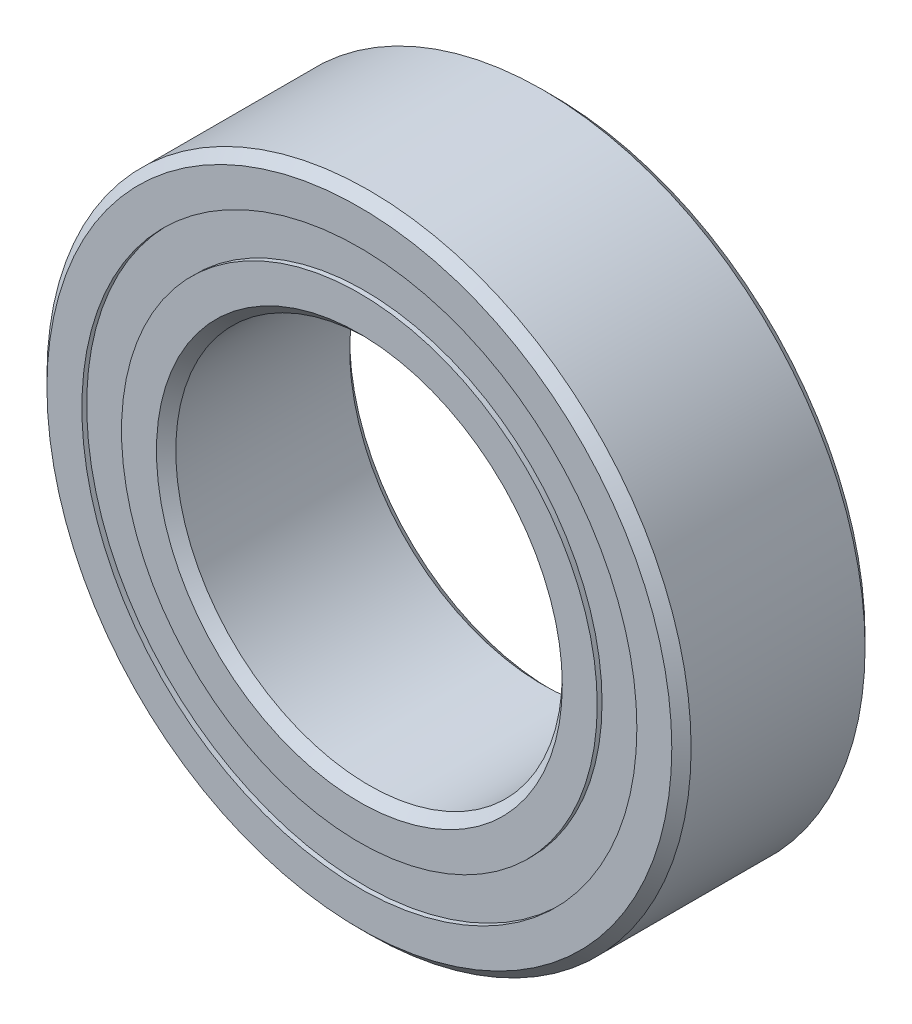
SolidWorks part; units mm, degrees
material "AISI 304"
ref_plane "Front Plane" through (0, 0, 0) normal (0, 0, 1) x (1, 0, 0)
ref_plane "Top Plane" through (0, 0, 0) normal (0, 1, 0) x (1, 0, 0)
ref_plane "Right Plane" through (0, 0, 0) normal (1, 0, 0) x (0, 0, -1)
sketch "Sketch1" plane through (0, 0, 0) normal (1, 0, 0) x (0, 0, -1)
  line L0 (-1.5, 0) -> (1.5, 0) construction
  line L1 (0, 5) -> (0, -5) construction
  line L2 (1.35, 5) -> (-1.35, 5)
  line L3 (-1.35, 5) -> (-1.5, 4.85)
  line L4 (-1.5, 4.85) -> (-1.5, 4.3077)
  line L5 (-1.5, 4.3077) -> (-0.6667, 4.3077)
  line L6 (1.5, 4.3077) -> (0.6667, 4.3077)
  line L7 (1.5, 4.85) -> (1.5, 4.3077)
  line L8 (1.35, 5) -> (1.5, 4.85)
  line L9 (0, 5) -> (0, 4) construction
  line L10 (0, 4) -> (0, 3) construction
  arc A0 (-0.6667, 4.3077) -> (0.6667, 4.3077) centre (0, 4) cw
  point P14 (0, 3)
  dimension "D3" = 1.3333
  dimension "D1" = 45
  dimension "Width" = 3
  dimension "OD" = 10
  dimension "D2" = 0.15
  dimension "Shaft Dia" = 6
  dimension "D4" = 0.3077
revolve "Revolve1" add sketch "Sketch1" angle 360 about L0
sketch "Sketch3" plane through (0, 0, 0) normal (1, 0, 0) x (0, 0, -1)
  line L0 (-1.5, 3.6923) -> (-0.6667, 3.6923)
  line L1 (0, 5) -> (0, -5) construction
  line L2 (-1.5, 4.85) -> (-1.5, 4.3077) construction
  line L3 (-1.5, 3.6923) -> (-1.5, 3.15)
  line L4 (-1.35, 5) -> (-1.5, 4.85) construction
  line L5 (-1.5, 3.15) -> (-1.35, 3)
  line L6 (-1.35, 3) -> (1.35, 3)
  line L7 (1.35, 5) -> (1.35, -5) construction
  line L8 (1.35, 3) -> (1.5, 3.15)
  line L9 (1.5, -4.85) -> (1.5, 4.85) construction
  line L10 (1.5, 3.15) -> (1.5, 3.6923)
  line L11 (1.5, 3.6923) -> (0.6667, 3.6923)
  line L13 (1.35, 5) -> (1.5, 4.85) construction
  arc A0 (0.6667, 4.3077) -> (-0.6667, 4.3077) centre (0, 4) ccw construction
  arc A1 (0.6667, 3.6923) -> (-0.6667, 3.6923) centre (0, 4) cw
revolve "Revolve3" add sketch "Sketch3" angle 360 about L0
sketch "Sketch4" plane through (0, 0, 0) normal (1, 0, 0) x (0, 0, -1)
  line L0 (-0.7342, 4) -> (0.7342, 4)
  arc A2 (-0.7342, 4) -> (0.7342, 4) centre (0, 4) cw
  arc A3 (0.6667, 4.3077) -> (-0.6667, 4.3077) centre (0, 4) ccw construction
revolve "Revolve4" add sketch "Sketch4" angle 360 about L0
ref_axis "Axis1" through (0, 0, -1.5) along (0, 0, 1)
pattern_circular "CirPattern1" count 12 every 30 about axis through (0, 0, -1.5) along (0, 0, 1) of bodies 104
sketch "Sketch5" plane through (0, 0, 0) normal (1, 0, 0) x (0, 0, -1)
  line L0 (-1.5, 4.3077) -> (-0.6667, 4.3077) construction
  line L1 (-1.425, 4.3077) -> (-0.7342, 4.3077)
  line L2 (-1.425, 4.3077) -> (-1.425, 3.6923)
  line L3 (-1.425, 3.6923) -> (-0.7342, 3.6923)
  line L4 (-0.7342, 4.3077) -> (-0.7342, 3.6923)
  line L5 (-1.5, 3.6923) -> (-0.6667, 3.6923) construction
  line L6 (1.5, 4.3077) -> (0.6667, 4.3077) construction
  line L7 (1.425, 4.3077) -> (0.7342, 4.3077)
  line L8 (1.425, 4.3077) -> (1.425, 3.6923)
  line L9 (1.425, 3.6923) -> (0.7342, 3.6923)
  line L10 (0.7342, 4.3077) -> (0.7342, 3.6923)
  line L11 (1.5, 3.6923) -> (0.6667, 3.6923) construction
  line L12 (-1.35, 5) -> (-1.5, 4.85) construction
  point P18 (-1.425, 4.925)
revolve "Revolve5" add sketch "Sketch5" angle 360 about L0
sketch "Sketch6" plane through (0, 0, 0) normal (1, 0, 0) x (0, 0, -1)
  line L0 (1.5, 0) -> (-1.5, 0) construction
  line L1 (1.5, 4.3077) -> (0.7126, 4.3077)
  line L2 (1.5, 4.3077) -> (1.5, 6.9469)
  line L3 (1.5, 6.9469) -> (0.7126, 6.9469)
  line L4 (0.7126, 4.3077) -> (0.7126, 6.9469)
  dimension "Th" = 0.7874
  dimension "Flange OD" = 13.8938
revolve "Revolve6" [suppressed] add sketch "Sketch6" angle 360 about L0
equation "\"D2@Sketch1\" = \"Width@Sketch1\"*.05"
equation "\"D3@Sketch1\" = \"Width@Sketch1\"/2.25"
equation "\"D4@Sketch1\" = (((\"OD@Sketch1\"-\"Width@Sketch1\")/2)/3.25)/3.5"
equation "\"D2@CirPattern1\" = 360/\"Balls@CirPattern1\""
